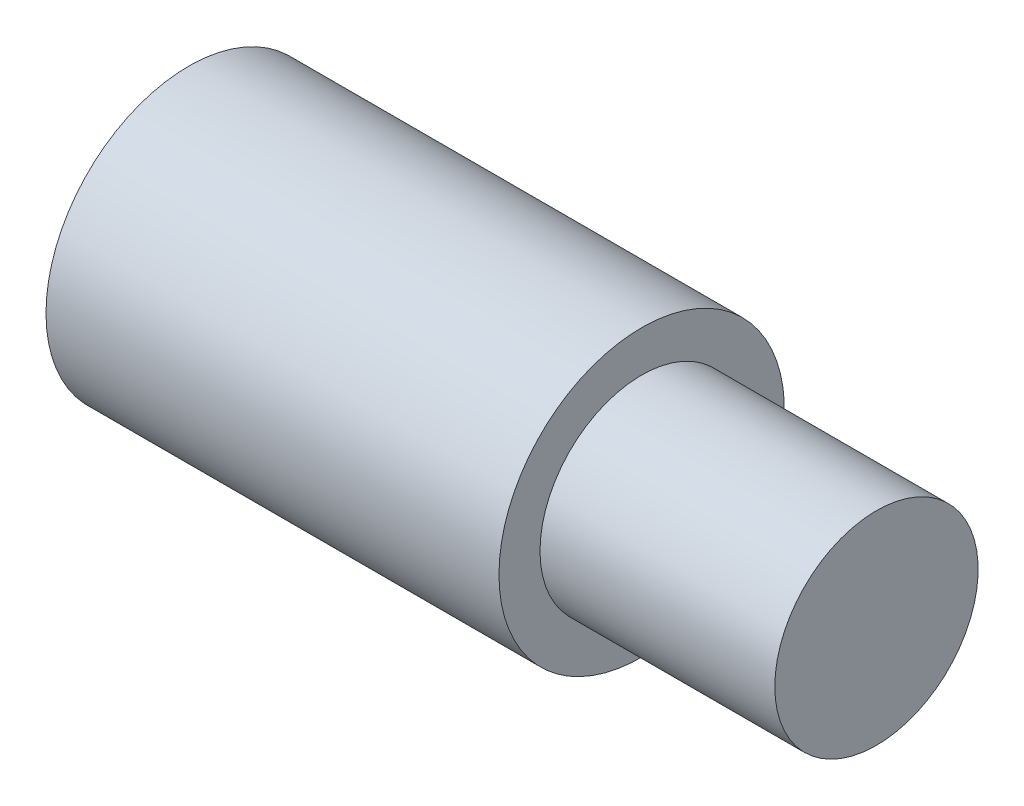
SolidWorks part; units mm, degrees
ref_plane "Front Plane" through (0, 0, 0) normal (0, 0, 1) x (1, 0, 0)
ref_plane "Top Plane" through (0, 0, 0) normal (0, 1, 0) x (1, 0, 0)
ref_plane "Right Plane" through (0, 0, 0) normal (1, 0, 0) x (0, 0, -1)
sketch "Conn_T4_MNPT Sketch" plane through (0, 0, 0) normal (0, 0, 1) x (1, 0, 0)
  line L0 (-1000, 0) -> (1000, 0) construction
  line L1 (12.7, 0) -> (12.7, 5.5)
  line L2 (12.7, 5.5) -> (0, 5.5)
  line L3 (0, 5.5) -> (0, 7.72)
  line L4 (0, 7.72) -> (-24.5, 7.72)
  line L5 (-24.5, 7.72) -> (-24.5, 0)
  line L6 (-24.5, 0) -> (12.7, 0)
revolve "Conn_T4_MNPT" add sketch "Conn_T4_MNPT Sketch" angle 360 about L0
ref_axis "Engine Axis" through (14.56, 0, 0) along (-1, 0, 0)
sketch "Socket 1 Sketch" plane through (0, 0, 0) normal (0, 0, 1) x (1, 0, 0)
  line L0 (-1000, 0) -> (1000, 0) construction
  line L1 (-25.5, 0) -> (-25.5, 3.175)
  line L2 (-25.5, 3.175) -> (-9.3, 3.175)
  line L3 (-9.3, 3.175) -> (-9.3, 0)
  line L4 (-9.3, 0) -> (-25.5, 0)
revolve "Socket 1" cut sketch "Socket 1 Sketch" angle 360 about L0
